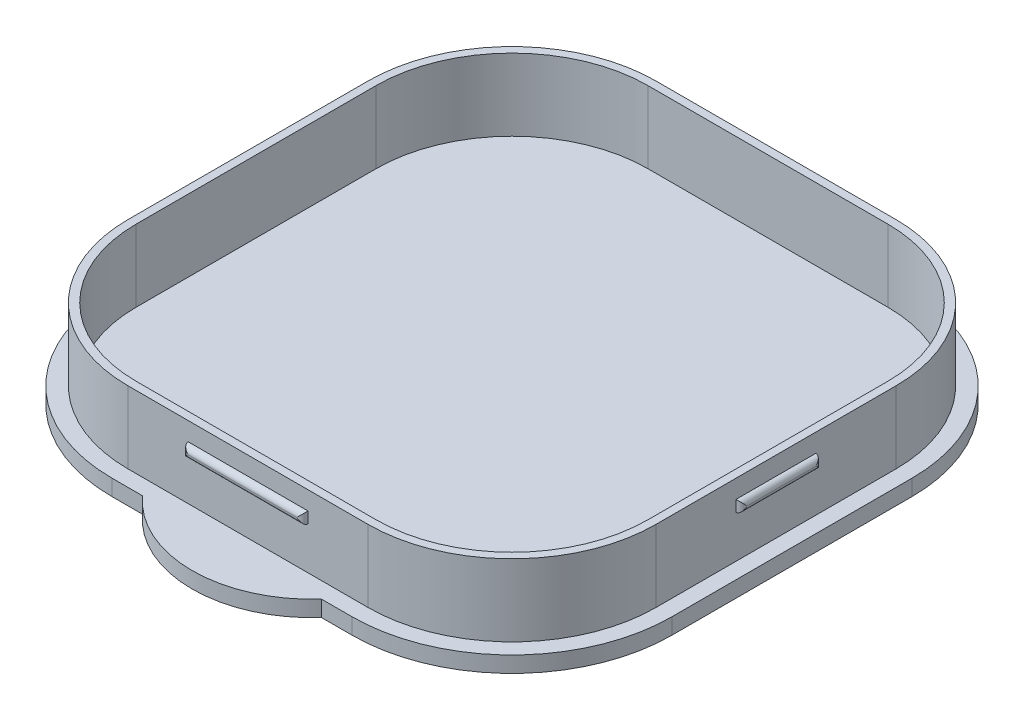
SolidWorks part; units mm, degrees
ref_plane "前视基准面" through (0, 0, 0) normal (0, 0, 1) x (1, 0, 0)
ref_plane "上视基准面" through (0, 0, 0) normal (0, 1, 0) x (1, 0, 0)
ref_plane "右视基准面" through (0, 0, 0) normal (1, 0, 0) x (0, 0, -1)
other "Configuration Table"
sketch "草图1" plane through (0, 0, 0) normal (0, 1, 0) x (1, 0, 0)
  line L0 (0, -1150) -> (0, -40) construction
  line L1 (-35, -35) -> (-11.1803, -35)
  line L2 (-35, -35) -> (-35, 35)
  line L3 (-35, 35) -> (-11.1803, 35)
  line L4 (35, -35) -> (35, 35)
  line L5 (-35, -35) -> (35, 35) construction
  line L6 (-35, 35) -> (35, -35) construction
  line L7 (0, 0) -> (71.6164, 0) construction
  line L8 (11.1803, 35) -> (35, 35)
  line L9 (0, 40) -> (0, 1099.1626) construction
  line L10 (11.1803, -35) -> (35, -35)
  line L11 (0, -70) -> (0, 70) construction
  arc A0 (-11.1803, 35) -> (11.1803, 35) centre (0, 25) cw
  arc A1 (-11.1803, -35) -> (11.1803, -35) centre (0, -25) ccw
  point P0 (0, 0)
  dimension "D4" = 15
  dimension "D1" = 70
  dimension "D2" = 70
  dimension "D3" = 10
  dimension "D5" = 22.3607
extrude "凸台-拉伸1" add sketch "草图1" along normal blind 2
fillet "圆角1" radius 20 4 edges at (-35, 1, 35) (-35, 1, -35) (35, 1, 35) (35, 1, -35)
sketch "草图2" plane through (0, 2, 0) normal (0, 1, 0) x (1, 0, 0)
  line L4 (-10.247, 33) -> (10.247, 33)
  line L5 (-10.247, -33) -> (10.247, -33)
  line L16 (-15, -33) -> (-10.247, -33)
  line L17 (33, -15) -> (33, 15)
  line L18 (-10.247, 33) -> (-15, 33)
  line L19 (-33, 15) -> (-33, -15)
  line L20 (-15, -33) -> (-10.247, -33)
  line L21 (33, -15) -> (33, 15)
  line L22 (-10.247, 33) -> (-15, 33)
  line L23 (-33, 15) -> (-33, -15)
  line L26 (10.247, -33) -> (15, -33)
  line L27 (10.247, -33) -> (15, -33)
  line L28 (15, 33) -> (10.247, 33)
  line L29 (15, 33) -> (10.247, 33)
  arc A16 (-10.247, -33) -> (10.247, -33) centre (0, -25) ccw
  arc A18 (-15, 33) -> (-33, 15) centre (-15, 15) ccw
  arc A19 (-33, -15) -> (-15, -33) centre (-15, -15) ccw
  arc A22 (-15, 33) -> (-33, 15) centre (-15, 15) ccw
  arc A23 (-33, -15) -> (-15, -33) centre (-15, -15) ccw
  arc A24 (10.247, 33) -> (-10.247, 33) centre (0, 25) ccw
  arc A28 (15, -33) -> (33, -15) centre (15, -15) ccw
  arc A29 (15, -33) -> (33, -15) centre (15, -15) ccw
  arc A30 (33, 15) -> (15, 33) centre (15, 15) ccw
  arc A31 (33, 15) -> (15, 33) centre (15, 15) ccw
  dimension "D1" = 2
extrude "凸台-拉伸2" add sketch "草图2" along normal blind 9
sketch "草图3" plane through (0, 11, 0) normal (0, 1, 0) x (1, 0, 0)
  line L28 (-15, -32) -> (15, -32)
  line L29 (32, -15) -> (32, 15)
  line L30 (15, 32) -> (-15, 32)
  line L31 (-32, 15) -> (-32, -15)
  line L32 (-15, -32) -> (15, -32)
  line L33 (32, -15) -> (32, 15)
  line L34 (15, 32) -> (-15, 32)
  line L35 (-32, 15) -> (-32, -15)
  arc A23 (-32, -15) -> (-15, -32) centre (-15, -15) ccw
  arc A30 (-15, 32) -> (-32, 15) centre (-15, 15) ccw
  arc A31 (-32, -15) -> (-15, -32) centre (-15, -15) ccw
  arc A34 (-15, 32) -> (-32, 15) centre (-15, 15) ccw
  arc A39 (15, -32) -> (32, -15) centre (15, -15) ccw
  arc A40 (15, -32) -> (32, -15) centre (15, -15) ccw
  arc A41 (32, 15) -> (15, 32) centre (15, 15) ccw
  arc A42 (32, 15) -> (15, 32) centre (15, 15) ccw
  dimension "D1" = 1
extrude "切除-拉伸2" cut sketch "草图3" against normal blind 9
sketch "草图4" plane through (-33, 0, 0) normal (-1, 0, 0) x (0, 0, 1)
  line L0 (-15, 6.5) -> (15, 6.5) construction
  line L1 (0, 11) -> (0, 2) construction
  line L3 (-5, 7.3) -> (5, 7.3)
  line L4 (-15, 2) -> (15, 2)
  line L5 (15, 2) -> (15, 11)
  line L6 (15, 11) -> (-15, 11)
  line L7 (-15, 11) -> (-15, 2)
  line L8 (-15, 2) -> (15, 2) construction
  line L9 (15, 2) -> (15, 11) construction
  line L10 (15, 11) -> (-15, 11) construction
  line L11 (-15, 11) -> (-15, 2) construction
  line L12 (-5, 7.3) -> (-5, 8.7)
  line L13 (-5, 8.7) -> (5, 8.7)
  line L14 (5, 7.3) -> (5, 8.7)
  line L15 (-5, 7.3) -> (5, 8.7) construction
  line L16 (-5, 8.7) -> (5, 7.3) construction
  point P8 (0, 8)
  point P13 (5, 9.0092)
  dimension "D2" = 1.4
  dimension "D3" = 0.8
  dimension "D4" = 10
  dimension "D1" = 0
extrude "凸台-拉伸3" add sketch "草图4" along normal blind 0.7
fillet "圆角2" radius 0.7 4 edges at (-33.7, 8, 5) (-33.7, 8, -5) (-33.7, 7.3, 0) (-33.7, 8.7, 0)
mirror "镜向1" about plane through (0, 0, 0) normal (1, 0, 0) of "凸台-拉伸3", "圆角2"
sketch "草图5" plane through (0, 0, 33) normal (0, 0, 1) x (1, 0, 0)
  line L0 (-15, 6.5) -> (15, 6.5) construction
  line L1 (0, 11) -> (0, 2) construction
  line L3 (-7.5, 7.3) -> (7.5, 7.3)
  line L4 (-15, 2) -> (15, 2)
  line L5 (15, 2) -> (15, 11)
  line L6 (15, 11) -> (-15, 11)
  line L7 (-15, 11) -> (-15, 2)
  line L8 (-15, 2) -> (15, 2) construction
  line L9 (15, 2) -> (15, 11) construction
  line L10 (15, 11) -> (-15, 11) construction
  line L11 (-15, 11) -> (-15, 2) construction
  line L12 (-7.5, 7.3) -> (-7.5, 8.7)
  line L13 (-7.5, 8.7) -> (7.5, 8.7)
  line L14 (7.5, 7.3) -> (7.5, 8.7)
  line L15 (-7.5, 7.3) -> (7.5, 8.7) construction
  line L16 (-7.5, 8.7) -> (7.5, 7.3) construction
  point P8 (0, 8)
  dimension "D2" = 1.4
  dimension "D3" = 15
  dimension "D4" = 0.8
  dimension "D1" = 0
extrude "凸台-拉伸4" add sketch "草图5" along normal blind 0.7
fillet "圆角3" radius 0.7 4 edges at (0, 7.3, 33.7) (-7.5, 8, 33.7) (0, 8.7, 33.7) (7.5, 8, 33.7)
mirror "镜向2" about plane through (0, 0, 0) normal (0, 0, 1) of "凸台-拉伸4", "圆角3"
